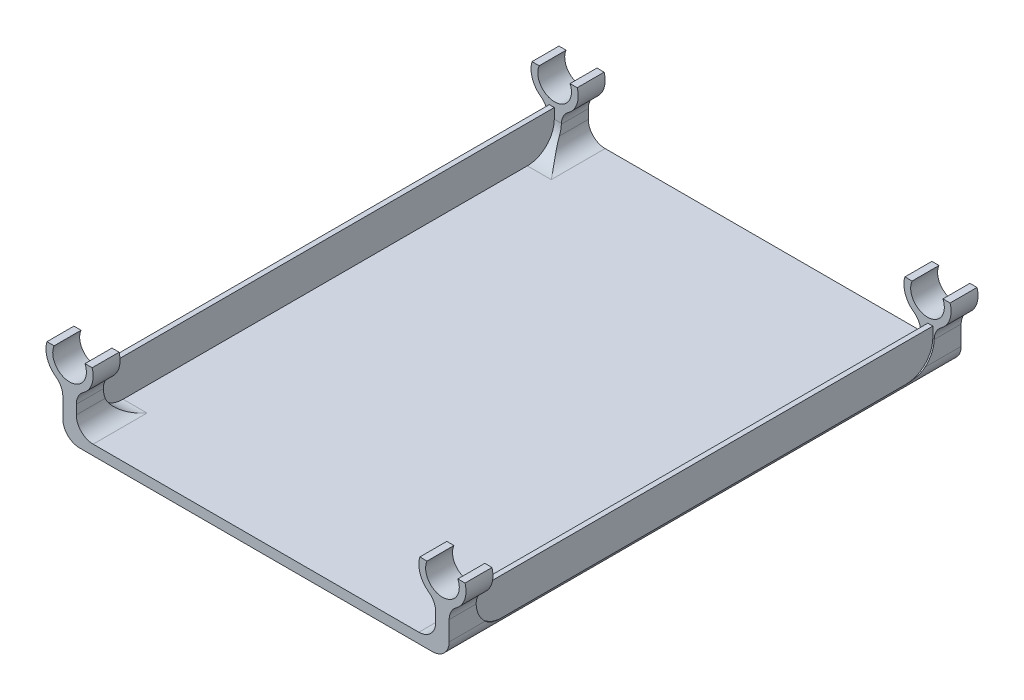
SolidWorks part; units mm, degrees
material "PLA 100% Infill"
ref_plane "Front Plane" through (0, 0, 0) normal (0, 0, 1) x (1, 0, 0)
ref_plane "Top Plane" through (0, 0, 0) normal (0, 1, 0) x (1, 0, 0)
ref_plane "Right Plane" through (0, 0, 0) normal (1, 0, 0) x (0, 0, -1)
sketch "Sketch1" plane through (0, 0, 0) normal (0, 0, 1) x (1, 0, 0)
  line L0 (-57.35, 0) -> (-57.35, 20.5) construction
  line L1 (0, 0) -> (-114.7, 0)
  line L2 (0, 0) -> (0, 2)
  line L3 (-4, 3) -> (-110.7, 3)
  line L4 (-114.7, 0) -> (-114.7, 2)
  line L5 (-53.0777, 20.5) -> (-61.6223, 20.5) construction
  line L6 (-114.7, 2) -> (-114.7, 13.7918)
  line L7 (-114.7, 13.7918) -> (-110.7, 13.7918) construction
  line L8 (-110.7, 13.7918) -> (-110.7, 3)
  line L9 (-119.4082, 22.5) -> (-117.2826, 22.5)
  line L10 (-108.1174, 22.5) -> (-105.9918, 22.5)
  line L11 (0, 2) -> (0, 13.7918)
  line L12 (-4, 13.7918) -> (-4, 3)
  line L13 (4.7082, 22.5) -> (2.5826, 22.5)
  line L14 (-6.5826, 22.5) -> (-8.7082, 22.5)
  line L15 (0, 13.7918) -> (0, 2)
  line L16 (-80.7757, 3) -> (-81.6086, 3)
  arc A0 (-117.2826, 22.5) -> (-108.1174, 22.5) centre (-112.7, 20.5) ccw
  arc A1 (-119.4082, 22.5) -> (-114.7, 13.7918) centre (-112.7, 20.5) ccw
  arc A2 (4.7082, 22.5) -> (0, 13.7918) centre (-2, 20.5) cw
  arc A3 (2.5826, 22.5) -> (-6.5826, 22.5) centre (-2, 20.5) cw
  arc A4 (-4, 13.7918) -> (-8.7082, 22.5) centre (-2, 20.5) cw
  arc A5 (-110.7, 13.7918) -> (-105.9918, 22.5) centre (-112.7, 20.5) ccw
  dimension "D2" = 10
  dimension "D6" = 3
  dimension "D1" = 20.5
  dimension "D3" = 114.7
  dimension "D4" = 2
  dimension "D5" = 4
  dimension "D7" = 2
  dimension "D8" = 2
extrude "Boss-Extrude1" add sketch "Sketch1" along normal blind 152 contours L8 A5 L10 A0 L9 A1 L6 L4 L1 L2 L11 A2 L13 A3 L14 A4 L12 L3 region at (-57.35, 1.2671, 0)
fillet "Fillet1" radius 5 8 edges at (0, 0, 76) (-114.7, 0, 76) (0, 13.7918, 76) (-4, 13.7918, 76) (-4, 3, 76) (-110.7, 3, 76) (-114.7, 13.7918, 76) (-110.7, 13.7918, 76)
sketch "Sketch2" plane through (-114.7, 0, 0) normal (-1, 0, 0) x (0, 0, 1)
  line L0 (152, 22.5) -> (0, 22.5) construction
  line L1 (8, 22.5) -> (144, 22.5)
  line L2 (8, 22.5) -> (8, 3)
  line L4 (144, 22.5) -> (144, 3)
  line L5 (0, 0) -> (-6.1147, 13.5)
  line L6 (-6.1147, 13.5) -> (-2.1147, 13.5)
  line L7 (-2.1147, 13.5) -> (1.8573, 4.7307)
  line L8 (8, 3) -> (144, 3)
  line L9 (152, 3) -> (0, 3) construction
  line L18 (76, 22.5) -> (76, 0) construction
  line L19 (152, 14.8144) -> (152, 22.5) construction
  line L21 (154.1147, 13.5) -> (150.1427, 4.7307)
  line L22 (158.1147, 13.5) -> (154.1147, 13.5)
  line L23 (152, 0) -> (158.1147, 13.5)
  line L24 (0, 0) -> (1.8573, 4.7307)
  line L25 (150.1427, 4.7307) -> (152, 0)
  line L26 (152, 0) -> (0, 0) construction
  line L27 (0, 22.5) -> (0, 14.8144) construction
  dimension "D1" = 8
  dimension "D2" = 8
  dimension "D6" = 4
  dimension "D7" = 13.5
extrude "Cut-Extrude1" cut sketch "Sketch2" against normal through all and the other way through all contours L2 L8 L4 L1
fillet "Fillet5" radius 8 4 edges at (-4.7087, 3, 8) (-4.7087, 3, 144) (-109.9913, 3, 144) (-109.9913, 3, 8)
ref_plane "Plane1" through (-114.2826, 0, 0) normal (-1, 0, 0) x (0, 0, 1)
sketch "Sketch4" plane through (0, 0, 8) normal (0, 0, 1) x (1, 0, 0)
  line L4 (-105.7, 3) -> (-114.2826, 3) construction
  line L5 (-114.2826, 61.8075) -> (-114.2826, -61.8075) construction
  line L6 (-57.35, 3) -> (-57.35, 0) construction
  line L7 (-114.2826, 14) -> (-112.7947, 14)
  line L8 (-114.2826, 14) -> (-114.2826, 3)
  line L9 (-114.2826, 3) -> (-112.7947, 3)
  line L10 (-112.7947, 14) -> (-112.7947, 3)
  line L11 (-114.2826, 14) -> (-112.7947, 3) construction
  line L12 (-114.2826, 3) -> (-112.7947, 14) construction
  line L13 (-9, 3) -> (-105.7, 3) construction
  line L14 (-5, 0) -> (-109.7, 0) construction
  line L15 (-1.9053, 14) -> (-1.9053, 3)
  line L16 (-0.4174, 3) -> (-1.9053, 3)
  line L17 (-0.4174, 14) -> (-0.4174, 3)
  line L18 (-0.4174, 14) -> (-1.9053, 14)
  arc A0 (-114.7, 5) -> (-109.7, 0) centre (-109.7, 5) ccw construction
  point P12 (-113.5386, 8.5)
  dimension "D1" = 11
extrude "Boss-Extrude5" add sketch "Sketch4" along normal up to surface (136 mm away) up to face at (-112.7, 16.783, 144)
